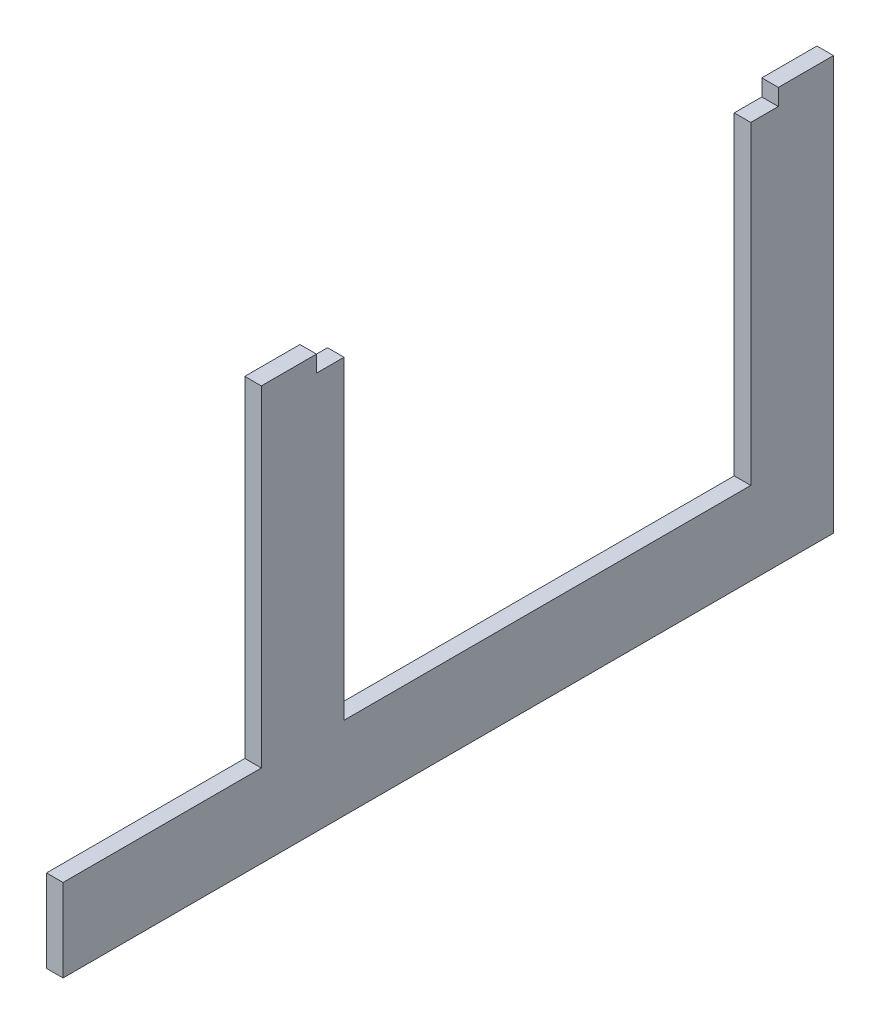
SolidWorks part; units mm, degrees
ref_plane "Front Plane" through (0, 0, 0) normal (0, 0, 1) x (1, 0, 0)
ref_plane "Top Plane" through (0, 0, 0) normal (0, 1, 0) x (1, 0, 0)
ref_plane "Right Plane" through (0, 0, 0) normal (1, 0, 0) x (0, 0, -1)
sketch "Sketch1" plane through (0, 0, 0) normal (0, 1, 0) x (1, 0, 0)
  line L0 (0, 0) -> (0, 103.7444) construction
  line L1 (-36.8722, 0) -> (36.8722, 0) construction
  line L2 (-36.8722, 0) -> (-36.8722, 103.7444)
  line L3 (-36.8722, 103.7444) -> (36.8722, 103.7444)
  line L4 (36.8722, 0) -> (36.8722, 103.7444)
  line L5 (36.8722, 103.7444) -> (36.8722, 0) construction
  line L6 (45.8722, 103.7444) -> (-45.8722, 103.7444) construction
  line L7 (21.0585, 67.686) -> (21.0585, 0)
  line L8 (-21.0585, 67.686) -> (-21.0585, 0)
  line L9 (-36.8722, 0) -> (-21.0585, 0)
  line L10 (21.0585, 0) -> (36.8722, 0)
  line L11 (31.8722, 103.7444) -> (31.8722, 88.7444) construction
  line L12 (34.8722, 103.7444) -> (34.8722, 88.7444) construction
  line L13 (31.8722, 93.7444) -> (34.8722, 93.7444) construction
  line L14 (31.8722, 10) -> (34.8722, 10) construction
  line L15 (31.8722, 88.7444) -> (34.8722, 88.7444) construction
  line L16 (31.8722, 15) -> (34.8722, 15) construction
  line L17 (31.8722, 15) -> (31.8722, 0) construction
  line L18 (34.8722, 15) -> (34.8722, 0) construction
  line L19 (33.3722, 93.7444) -> (33.3722, 88.7444) construction
  line L20 (33.3722, 15) -> (33.3722, 10) construction
  line L21 (34.8722, 100.7444) -> (-34.8722, 100.7444) construction
  line L22 (-34.8722, 100.7444) -> (-34.8722, 103.7444) construction
  line L23 (56.7, -65.95) -> (59.7, -65.95) construction
  arc A0 (21.0585, 67.686) -> (-21.0585, 67.686) centre (0, 67.686) ccw construction
  arc A1 (21.0585, 67.686) -> (-21.0585, 67.686) centre (0, 67.686) ccw
  circle A2 centre (26.5585, 78.4307) radius 1.6 construction
  circle A3 centre (-26.5585, 78.4307) radius 1.6 construction
  circle A4 centre (26.5585, 25.3138) radius 1.6 construction
  circle A5 centre (-26.5585, 25.3138) radius 1.6 construction
  circle A6 centre (26.5585, 78.4307) radius 1.6
  circle A7 centre (-26.5585, 78.4307) radius 1.6
  circle A8 centre (26.5585, 25.3138) radius 1.6
  circle A9 centre (-26.5585, 25.3138) radius 1.6
  dimension "D2" = 2
  dimension "D3" = 10
  dimension "D4" = 5
ref_plane "Plane1" through (34.8722, 0, 0) normal (1, 0, 0) x (0, 0, -1)
sketch "Sketch2" plane through (34.8722, 0, 0) normal (1, 0, 0) x (0, 0, -1)
  line L0 (103.7444, 3) -> (103.7444, -72)
  line L1 (103.7444, -72) -> (-35.95, -72)
  line L2 (0, -57) -> (0, 3)
  line L3 (0, 3) -> (10, 3)
  line L4 (10, 3) -> (10, 0)
  line L5 (10, 0) -> (15, 0)
  line L6 (15, 0) -> (15, -57)
  line L7 (15, -57) -> (88.7444, -57)
  line L8 (88.7444, -57) -> (88.7444, 0)
  line L9 (88.7444, 0) -> (93.7444, 0)
  line L10 (93.7444, 0) -> (93.7444, 3)
  line L11 (93.7444, 3) -> (103.7444, 3)
  line L12 (103.7444, 0) -> (88.7444, 0) construction
  line L13 (93.7444, 0) -> (103.7444, 0) construction
  line L14 (98.7444, 0) -> (98.7444, 3) construction
  line L15 (-35.95, -72) -> (-65.95, -72) construction
  line L16 (15, 0) -> (0, 0) construction
  line L17 (100.7444, 0) -> (103.7444, 0) construction
  line L18 (103.7444, -46) -> (0, -46) construction
  line L19 (-65.95, -72) -> (-65.95, -57) construction
  line L20 (-65.95, -44.7) -> (-65.95, 65.6444) construction
  line L21 (-35.95, -72) -> (-35.95, -57)
  line L22 (-35.95, -57) -> (-65.95, -57) construction
  line L23 (0, -57) -> (-35.95, -57)
  dimension "D1" = 46
  dimension "D2" = 72
  dimension "D3" = 15
  dimension "D4" = 30
extrude "Boss-Extrude1" add sketch "Sketch2" against normal up to vertex (3 mm away) up to point (31.8722, 0, -103.7444)
